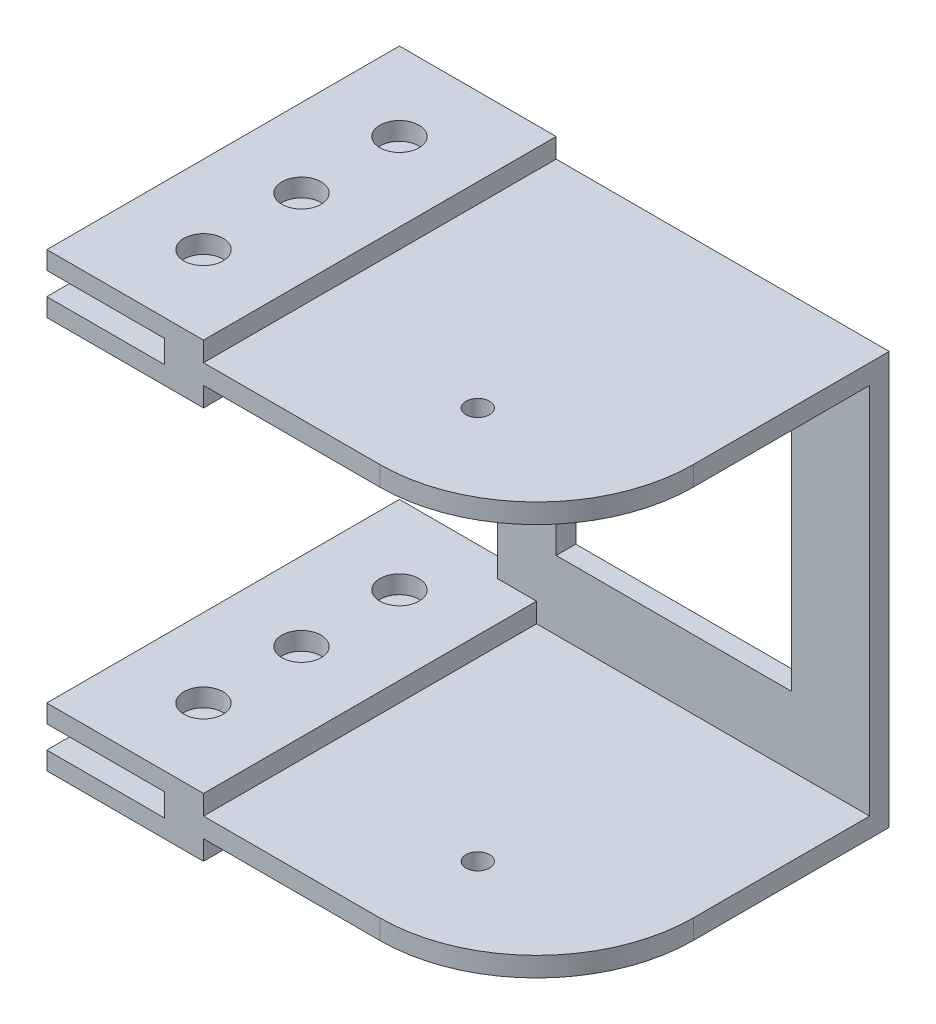
SolidWorks part; units mm, degrees
ref_plane "정면" through (0, 0, 0) normal (0, 0, 1) x (1, 0, 0)
ref_plane "윗면" through (0, 0, 0) normal (0, 1, 0) x (1, 0, 0)
ref_plane "우측면" through (0, 0, 0) normal (1, 0, 0) x (0, 0, -1)
sketch "스케치1" plane through (0, 0, 0) normal (0, 0, 1) x (1, 0, 0)
  line L0 (-30, -47.6) -> (90, -47.6)
  line L1 (90, -52.6) -> (-30, -52.6)
  line L2 (75, -47.6) -> (35, -47.6)
  line L3 (90, -47.6) -> (95, -47.6)
  line L4 (95, 47.6) -> (-30, 47.6)
  line L5 (95, -47.6) -> (95, 47.6)
  line L6 (0, -52.6) -> (0, 52.6)
  line L7 (-30, 52.6) -> (95, 52.6)
  line L8 (95, 52.6) -> (95, 47.6)
  line L9 (10, 42.6) -> (-30, 42.6)
  line L10 (-30, 42.6) -> (-30, 47.6)
  line L11 (-30, 47.6) -> (10, 47.6)
  line L12 (10, 47.6) -> (10, 42.6)
  line L13 (10, 52.6) -> (-30, 52.6)
  line L14 (-30, 52.6) -> (-30, 57.6)
  line L15 (-30, 57.6) -> (10, 57.6)
  line L16 (10, 57.6) -> (10, 52.6)
  line L17 (-50, 0) -> (95, 0) construction
  line L18 (10, -42.6) -> (-30, -42.6)
  line L19 (-30, -42.6) -> (-30, -47.6)
  line L20 (-30, -47.6) -> (10, -47.6)
  line L21 (10, -47.6) -> (10, -42.6)
  line L22 (10, -52.6) -> (-30, -52.6)
  line L23 (-30, -52.6) -> (-30, -57.6)
  line L24 (-30, -57.6) -> (10, -57.6)
  line L25 (10, -57.6) -> (10, -52.6)
  line L26 (90, -52.6) -> (95, -52.6)
  line L27 (95, -52.6) -> (95, -47.6)
extrude "보스-돌출1" add sketch "스케치1" against normal blind 5 contours L6 L17 L5 L4 L12 L9 | L17 L6 L18 L21 L0 L3 L5 | L26 L27 L3 L0 L6 L1 | L0 L21 L18 L6 | L18 L19 L0 L6 | L24 L25 L1 L23 | L10 L9 L6 L4 | L16 L15 L14 L7 | L8 L7 L6 L4 | L12 L4 L6 L9 region at (47.9752, -23.5619, 0) region at (47.5, -50.1, 0) region at (5, -45.1, 0) region at (-15, -45.1, 0) region at (-10, -55.1, 0) region at (47.9752, 23.5619, 0) region at (-15, 45.1, 0) region at (5, 45.1, 0) region at (47.5, 50.1, 0) region at (-10, 55.1, 0)
extrude "보스-돌출2" add sketch "스케치1<3>" along normal blind 85 contours L8 L7 L6 L4 | L16 L15 L14 L7 | L12 L4 L6 L9 | L10 L9 L6 L4 | L0 L21 L18 L6 | L18 L19 L0 L6 | L24 L25 L1 L23 | L26 L27 L3 L0 L6 L1 region at (47.5, -50.1, 0) region at (5, -45.1, 0) region at (-15, -45.1, 0) region at (-10, -55.1, 0) region at (-15, 45.1, 0) region at (5, 45.1, 0) region at (47.5, 50.1, 0) region at (-10, 55.1, 0)
sketch "스케치1<3>" plane through (0, 0, 0) normal (0, 0, 1) x (1, 0, 0) same geometry as "스케치1"
sketch "스케치2" plane through (0, -52.6, 0) normal (0, -1, 0) x (1, 0, 0)
  line L0 (95, -5) -> (95, 85) construction
  line L1 (10, -5) -> (95, -5) construction
  circle A0 centre (55, 60) radius 3
  dimension "D3" = 6
  dimension "D1" = 40
  dimension "D2" = 65
extrude "컷-돌출1" cut sketch "스케치2" against normal blind 144
fillet "필렛1" radius 40 2 edges at (95, 50.1, 85) (95, -50.1, 85)
sketch "스케치4" plane through (0, 0, 85) normal (0, 0, 1) x (1, 0, 0)
  line L0 (-30, -52.6) -> (-30, -57.6) construction
  line L1 (-30, -53) -> (0, -53)
  line L2 (-30, -53) -> (-30, -47.2)
  line L3 (-30, -47.2) -> (0, -47.2)
  line L4 (0, -53) -> (0, -47.2)
  line L5 (-30, 42.6) -> (-30, 47.6) construction
  line L6 (-30, 47.2) -> (0, 47.2)
  line L7 (-30, 47.2) -> (-30, 53)
  line L8 (-30, 53) -> (0, 53)
  line L9 (0, 47.2) -> (0, 53)
  line L10 (0, 47.6) -> (0, 52.6) construction
  line L11 (0, -52.6) -> (0, -47.6) construction
  line L12 (-30, -47.6) -> (0, -47.6) construction
  line L13 (0, -52.6) -> (-30, -52.6) construction
  line L14 (-30, 52.6) -> (0, 52.6) construction
  line L15 (0, 47.6) -> (-30, 47.6) construction
  dimension "D1" = 0.4
  dimension "D2" = 0.4
  dimension "D3" = 0.4
  dimension "D4" = 0.4
extrude "컷-돌출2" cut sketch "스케치4" against normal blind 144
sketch "스케치5" plane through (0, 0, 0) normal (0, 0, 1) x (1, 0, 0)
  line L1 (15, -30) -> (75, -30)
  line L2 (15, -30) -> (15, 30)
  line L3 (15, 30) -> (75, 30)
  line L4 (75, -30) -> (75, 30)
  line L5 (15, -30) -> (75, 30) construction
  line L6 (15, 30) -> (75, -30) construction
  point P0 (45, 0)
  dimension "D1" = 60
  dimension "D2" = 60
  dimension "D3" = 45
extrude "컷-돌출3" cut sketch "스케치5" against normal blind 144
sketch "스케치6" plane through (0, -57.6, 0) normal (0, -1, 0) x (1, 0, 0)
  line L0 (-10, 85) -> (-10, -5) construction
  line L1 (-30, 85) -> (10, 85) construction
  line L2 (-30, -5) -> (10, -5) construction
  circle A0 centre (-10, 40) radius 5
  circle A1 centre (-10, 65) radius 5
  circle A2 centre (-10, 15) radius 5
  dimension "D1" = 10
  dimension "D2" = 10
  dimension "D3" = 10
  dimension "D4" = 25
  dimension "D5" = 25
extrude "컷-돌출4" cut sketch "스케치6" against normal blind 144
